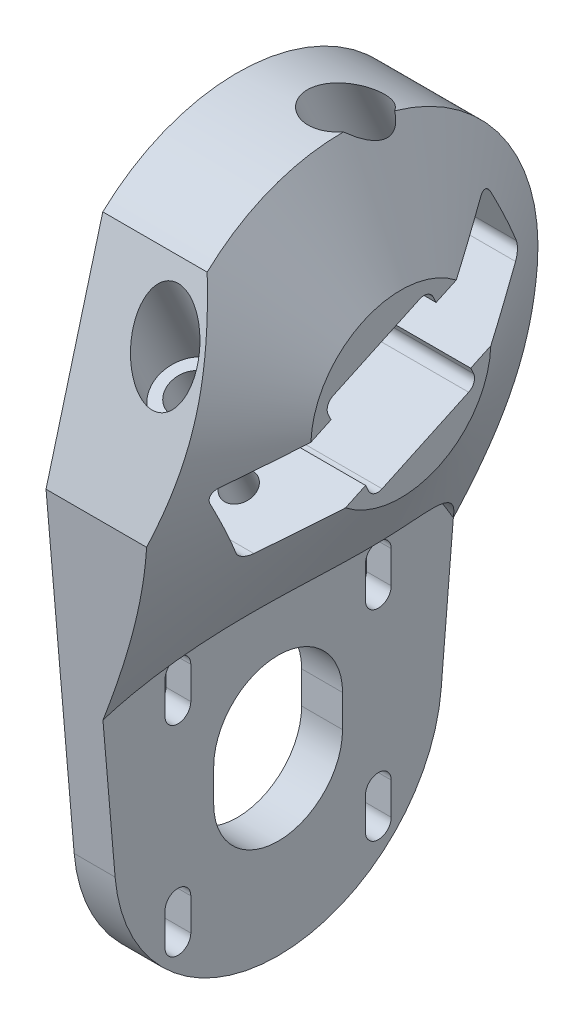
SolidWorks part; units mm, degrees
ref_plane "Front Plane" through (0, 0, 0) normal (0, 0, 1) x (1, 0, 0)
ref_plane "Top Plane" through (0, 0, 0) normal (0, 1, 0) x (1, 0, 0)
ref_plane "Right Plane" through (0, 0, 0) normal (1, 0, 0) x (0, 0, -1)
sketch "Sketch1" plane through (0, 0, 0) normal (1, 0, 0) x (0, 0, -1)
  line L0 (4.3532, 11.9603) -> (-11.9603, 4.3532)
  line L1 (4.3532, 11.9603) -> (11.9603, -4.3532)
  line L2 (-11.9603, 4.3532) -> (-4.3532, -11.9603)
  line L3 (11.9603, -4.3532) -> (-4.3532, -11.9603)
  line L4 (4.3532, 11.9603) -> (-4.3532, -11.9603) construction
  line L5 (-11.9603, 4.3532) -> (11.9603, -4.3532) construction
  line L6 (0, 0) -> (0, -57.15) construction
  line L7 (-30.3693, -2.5958) -> (-25.3077, -61.8132)
  line L8 (25.3077, -61.8132) -> (30.3693, -2.5958)
  line L9 (0, -57.15) -> (0, -103.9417) construction
  arc A0 (30.3693, -2.5958) -> (-30.3693, -2.5958) centre (0, 0) ccw
  arc A1 (-25.3077, -61.8132) -> (25.3077, -61.8132) centre (0, -59.65) ccw
  dimension "D1" = 2.5
  dimension "D2" = 30.48
  dimension "D6" = 57.15
  dimension "D7" = 25.4
  dimension "D8" = 0
  dimension "D3" = 18
  dimension "D4" = 18
  dimension "D5" = 25
extrude "Boss-Extrude1" add sketch "Sketch1" along normal blind 6.35 contours L7 A0 L1 L3 L2 L0 region at (0, -27.1671, 0)
sketch "Sketch19" plane through (6.35, 0, 0) normal (1, 0, 0) x (0, 0, -1)
  line L0 (0, -59.65) -> (0, -54.65)
  line L1 (0, -54.65) -> (15.5563, -39.0937) construction
  line L2 (15.5563, -44.0937) -> (15.5563, -39.0937) construction
  line L3 (13.5563, -44.0937) -> (13.5563, -39.0937)
  line L4 (17.5563, -44.0937) -> (17.5563, -39.0937)
  line L5 (-10, -59.65) -> (-10, -54.65)
  line L6 (10, -59.65) -> (10, -54.65)
  line L7 (0, -57.15) -> (7.4061, -57.15) construction
  line L8 (15.5563, -44.0937) -> (0, -59.65) construction
  line L9 (17.5563, -70.2063) -> (17.5563, -75.2063)
  line L10 (13.5563, -70.2063) -> (13.5563, -75.2063)
  line L11 (-17.5563, -44.0937) -> (-17.5563, -39.0937)
  line L12 (-13.5563, -44.0937) -> (-13.5563, -39.0937)
  line L13 (-13.5563, -70.2063) -> (-13.5563, -75.2063)
  line L14 (-17.5563, -70.2063) -> (-17.5563, -75.2063)
  line L15 (-15.5563, -44.0937) -> (0, -59.65) construction
  line L16 (0, -59.65) -> (-15.5563, -75.2063) construction
  line L17 (0, -59.65) -> (15.5563, -75.2063) construction
  arc A0 (-25.3077, -61.8132) -> (25.3077, -61.8132) centre (0, -59.65) ccw construction
  arc A1 (-25.3077, -61.8132) -> (25.3077, -61.8132) centre (0, -59.65) ccw
  arc A2 (-10, -59.65) -> (10, -59.65) centre (0, -59.65) ccw
  arc A3 (17.5563, -75.2063) -> (13.5563, -75.2063) centre (15.5563, -75.2063) cw
  arc A4 (13.5563, -70.2063) -> (17.5563, -70.2063) centre (15.5563, -70.2063) cw
  arc A6 (17.5563, -39.0937) -> (13.5563, -39.0937) centre (15.5563, -39.0937) ccw
  arc A7 (13.5563, -44.0937) -> (17.5563, -44.0937) centre (15.5563, -44.0937) ccw
  arc A8 (-17.5563, -39.0937) -> (-13.5563, -39.0937) centre (-15.5563, -39.0937) cw
  arc A9 (10, -54.65) -> (-10, -54.65) centre (0, -54.65) ccw
  arc A10 (-13.5563, -44.0937) -> (-17.5563, -44.0937) centre (-15.5563, -44.0937) cw
  arc A11 (-13.5563, -70.2063) -> (-17.5563, -70.2063) centre (-15.5563, -70.2063) ccw
  arc A13 (-17.5563, -75.2063) -> (-13.5563, -75.2063) centre (-15.5563, -75.2063) ccw
  point P8 (0, -57.15)
  dimension "D1" = 135
  dimension "D3" = 22
  dimension "D5" = 4
  dimension "D6" = 5
  dimension "D4" = 4
  dimension "D8" = 0
  dimension "D2" = 5
  dimension "D7" = 45
extrude "Cut-Extrude18" cut sketch "Sketch19" against normal blind 10 contours L6 A9 L5 A2 | A10 L12 A8 L11 | L14 A13 L13 A11 | A4 L10 A3 L9 | L4 A6 L3 A7 region at (6.35, -57.15, 9.6798) region at (6.35, -72.7063, -15.5563) region at (6.35, -41.5937, 15.5563) region at (6.35, -72.7063, 15.5563)
sketch "Sketch20" plane through (6.35, 0, 0) normal (1, 0, 0) x (0, 0, -1)
  circle A0 centre (0, 0) radius 57.15
  arc A1 (-25.3077, -61.8132) -> (25.3077, -61.8132) centre (0, -59.65) ccw construction
  point P3 (0, -85.05)
extrude "Boss-Extrude5" add sketch "Sketch20" along normal blind 19.05
sketch "Sketch21" plane through (0, 0, 0) normal (-1, 0, 0) x (0, 0, 1)
  line L0 (-24.435, 4.3878) -> (-10.8404, -1.9515)
  line L1 (11.9603, 4.3532) -> (4.3532, -11.9603) construction
  line L3 (-4.3532, 11.9603) -> (-11.9603, -4.3532) construction
  line L4 (-4.3532, 11.9603) -> (11.9603, 4.3532) construction
  line L5 (11.9603, 4.3532) -> (10.8404, 1.9515)
  line L7 (-4.3532, 11.9603) -> (-5.4731, 9.5586)
  line L8 (-4.3532, 11.9603) -> (11.9603, 4.3532)
  line L9 (-21.7514, 10.1428) -> (-25.3766, 11.8333) construction
  line L10 (19.0678, -15.8979) -> (5.4731, -9.5586)
  line L11 (19.0678, -15.8979) -> (24.435, -4.3878)
  line L12 (-24.435, 4.3878) -> (-19.0678, 15.8979)
  line L13 (24.435, -4.3878) -> (10.8404, 1.9515)
  line L16 (4.3532, -11.9603) -> (5.4731, -9.5586)
  line L17 (-11.9603, -4.3532) -> (-10.8404, -1.9515)
  line L18 (11.9603, 4.3532) -> (-4.3532, 11.9603)
  line L21 (-10.8404, -1.9515) -> (-11.9603, -4.3532)
  line L24 (-10.8404, -1.9515) -> (-24.435, 4.3878)
  line L27 (-5.4731, 9.5586) -> (-4.3532, 11.9603)
  line L29 (-5.4731, 9.5586) -> (-19.0678, 15.8979)
  line L30 (5.4731, -9.5586) -> (4.3532, -11.9603)
  line L31 (10.8404, 1.9515) -> (11.9603, 4.3532)
  line M13 (-11.9603, -4.3532) -> (-4.3532, 11.9603)
  line M14 (-4.3532, 11.9603) -> (11.9603, 4.3532)
  line M15 (11.9603, 4.3532) -> (4.3532, -11.9603)
  line M16 (4.3532, -11.9603) -> (-11.9603, -4.3532)
  dimension "D1" = 15
  dimension "D2" = 12.7
extrude "Cut-Extrude14" cut sketch "Sketch21" against normal through all contours L29 L12 L0 M13 | M13 M16 M15 M14 | L11 L13 L10 M15 region at (0, 6.9732, -14.9541) region at (0, 0, 0) region at (0, -6.9732, 14.9541)
sketch "Sketch22" plane through (0, 5.7551, 2.6836) normal (0, -0.9063, -0.4226) x (-1, 0, 0)
  line L0 (-25.4, -9) -> (0, -9) construction
  line L2 (0, -28.6209) -> (0, 30.48) construction
  circle A0 centre (-12.5, -16.5) radius 3.175
  dimension "D2" = 12.5
  dimension "D3" = 6.35
  dimension "D1" = 7.5
extrude "Cut-Extrude15" cut sketch "Sketch22" against normal through all
ref_plane "Plane1" through (0, 10.3591, 4.8305) normal (0, -0.9063, -0.4226) x (-1, 0, 0)
sketch "Sketch24" plane through (0, 10.3591, 4.8305) normal (0, -0.9063, -0.4226) x (-1, 0, 0)
  circle A0 centre (-12.5, -16.5) radius 5
  dimension "D1" = 10
extrude "Cut-Extrude16" cut sketch "Sketch24" against normal through all
sketch "Sketch25" plane through (0, -5.7551, -2.6836) normal (0, 0.9063, 0.4226) x (1, 0, 0)
  circle A0 centre (12.5, -16.5) radius 3.175 construction
  circle A1 centre (12.5, -16.5) radius 3.175
  circle A2 centre (12.5, -16.5) radius 2.3813
  dimension "D1" = 0.7937
extrude "Cut-Extrude17" cut sketch "Sketch25" against normal blind 10 contours A2 region at (12.5, -12.7283, 12.2705)
ref_plane "Plane2" through (0, 0, 0) normal (0, 0.4226, -0.9063) x (-1, 0, 0)
mirror "Mirror1" about plane through (0, 0, 0) normal (0, 0.4226, -0.9063) of "Cut-Extrude17", "Cut-Extrude15", "Cut-Extrude16"
mirror "Mirror2" about plane through (0, 0, 0) normal (1, 0, 0) of bodies 124 126
delete or keep bodies "Body-Delete/Keep 1" type delete bodies bodies 127
chamfer "Chamfer2" distance 2.5 angle 45 8 edges at (0, -46.0937, 15.5563) (0, -41.5937, 13.5563) (0, -37.0937, 15.5563) (0, -41.5937, 17.5563) (0, -46.0937, -15.5563) (0, -41.5937, -17.5563) (0, -41.5937, -13.5563) (0, -37.0937, -15.5563)
sketch "Sketch26" plane through (0, 0, 0) normal (-1, 0, 0) x (0, 0, 1)
  line L0 (11.4538, -58.2291) -> (27.0119, -8.4408)
  line L1 (0, 0) -> (0, -54.65) construction
  circle A0 centre (0, -54.65) radius 12
  circle A1 centre (0, 0) radius 28.3
  dimension "D1" = 24
  dimension "D2" = 56.6
fillet "Fillet1" radius 1.5875 8 edges at (12.7, -4.3532, -11.9603) (12.7, 4.3878, -24.435) (12.7, 11.9603, -4.3532) (12.7, 15.8979, -19.0678) (12.7, -4.3878, 24.435) (12.7, 4.3532, 11.9603) (12.7, -11.9603, 4.3532) (12.7, -15.8979, 19.0678)
sketch "Sketch28" plane through (6.35, 0, 0) normal (1, 0, 0) x (0, 0, -1)
  arc A0 (-10, -54.65) -> (10, -54.65) centre (0, -54.65) ccw construction
  arc A1 (-10, -54.65) -> (10, -54.65) centre (0, -54.65) ccw
  circle A3 centre (0, -54.65) radius 31
  dimension "D1" = 62
extrude "Cut-Extrude19" cut sketch "Sketch28" along normal through all contours A3
sketch "Sketch29" plane through (25.4, 0, 0) normal (1, 0, 0) x (0, 0, -1)
  arc A1 (30.3693, -2.5958) -> (-30.3693, -2.5958) centre (0, 0) ccw construction
  arc A2 (30.3693, -2.5958) -> (-30.3693, -2.5958) centre (0, 0) ccw
  circle A3 centre (0, 0) radius 13.97
sketch "Sketch30" plane through (6.35, 0, 0) normal (1, 0, 0) x (0, 0, -1)
  circle A0 centre (0, 0) radius 48.173
sketch "Sketch31" plane through (0, 0, 0) normal (0, 1, 0) x (1, 0, 0)
  line L0 (25.4, -13.97) -> (25.4, 13.97) construction
  line L1 (25.4, -13.97) -> (25.4, 13.97)
  line L2 (6.35, -48.173) -> (6.35, 48.173) construction
  line L3 (6.35, -48.173) -> (6.35, 48.173)
  line L4 (25.4, -13.97) -> (6.35, -48.173)
  line L5 (6.35, -48.173) -> (6.35, -59.9521)
  line L6 (6.35, -59.9521) -> (25.4, -59.9521)
  line L7 (25.4, -59.9521) -> (25.4, -13.97)
  line L8 (25.4, 0) -> (0, 0) construction
revolve "Cut-Revolve1" cut sketch "Sketch31" angle 360 about L8 region at (17.7551, 0, 43.824)
sketch "Sketch32" plane through (6.35, 0, 0) normal (-1, 0, 0) x (0, 0, 1)
  line L0 (30.3693, -2.5958) -> (25.3077, -61.8132) construction
  line L1 (-25.3077, -61.8132) -> (-30.3693, -2.5958) construction
  line L2 (30.3693, -2.5958) -> (25.3077, -61.8132)
  line L3 (-25.3077, -61.8132) -> (-30.3693, -2.5958)
  arc A0 (30.3693, -2.5958) -> (-30.3693, -2.5958) centre (0, 0) ccw construction
  arc A1 (30.3693, -2.5958) -> (-30.3693, -2.5958) centre (0, 0) ccw
  circle A2 centre (0, 0) radius 48.173 construction
  circle A3 centre (0, 0) radius 48.173
  arc M2 (27.1923, -39.7645) -> (-27.1923, -39.7645) centre (0, 0) ccw
  line M3 (-27.1923, -39.7645) -> (-30.3693, -2.5958)
  arc M4 (-30.3693, -2.5958) -> (30.3693, -2.5958) centre (0, 0) cw
  line M5 (30.3693, -2.5958) -> (27.1923, -39.7645)
extrude "Cut-Extrude20" cut sketch "Sketch32" against normal through all contours M5 M2 M3 M4 region at (6.35, 31.7844, 0)
sketch "Sketch33" plane through (0, 0, 0) normal (-1, 0, 0) x (0, 0, 1)
  line L0 (30.3693, -2.5958) -> (25.3077, -61.8132) construction
  line L1 (30.3693, -2.5958) -> (25.3077, -61.8132)
  line L2 (29.6796, -10.6648) -> (20.8695, 22.2147)
  line L3 (22.9962, -3.7169) -> (10.8404, 1.9515) construction
  arc A0 (30.3693, -2.5958) -> (-30.3693, -2.5958) centre (0, 0) ccw construction
  arc A1 (30.3693, -2.5958) -> (-30.3693, -2.5958) centre (0, 0) ccw
  arc M35 (30.3693, -2.5958) -> (-30.3693, -2.5958) centre (0, 0) ccw
  dimension "D1" = 50
  dimension "D2" = 25.908
extrude "Cut-Extrude21" cut sketch "Sketch33" against normal through all contours L2 L1 M35 region at (0, 6.8897, 26.8598)
equation "\".75i\"=14.27"
